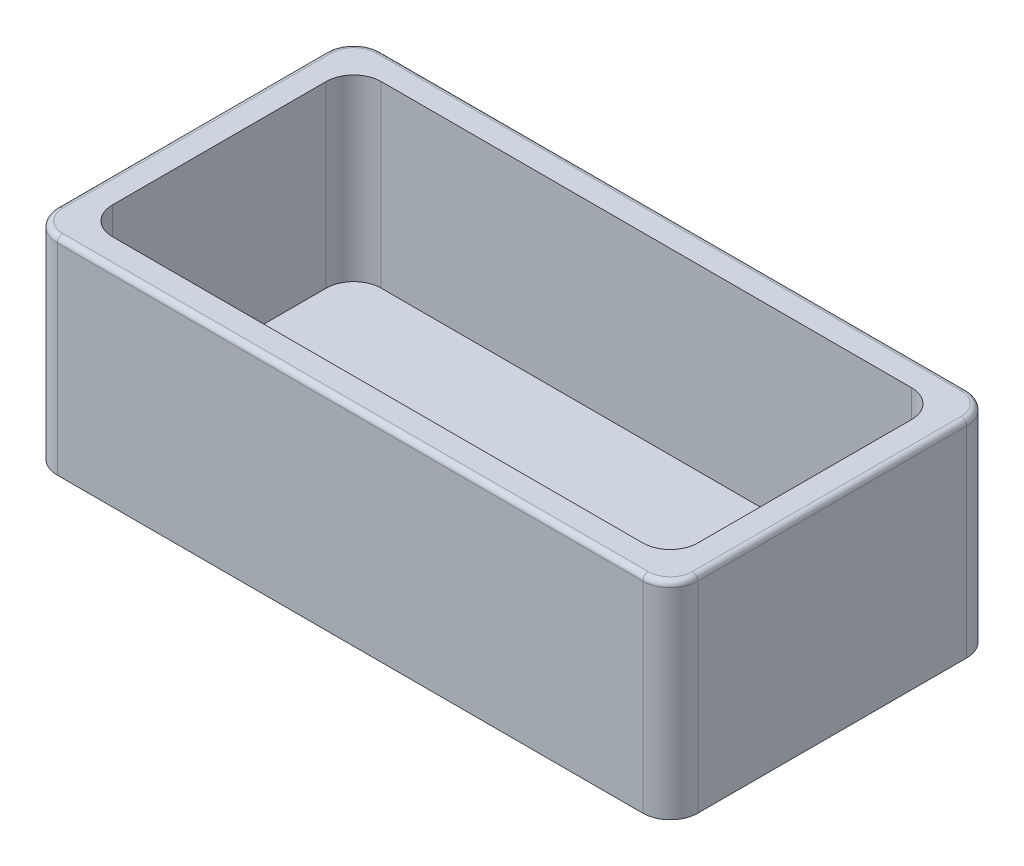
SolidWorks part; units mm, degrees
ref_plane "Front Plane" through (0, 0, 0) normal (0, 0, 1) x (1, 0, 0)
ref_plane "Top Plane" through (0, 0, 0) normal (0, 1, 0) x (1, 0, 0)
ref_plane "Right Plane" through (0, 0, 0) normal (1, 0, 0) x (0, 0, -1)
sketch "Sketch1" plane through (0, 0, 0) normal (0, 1, 0) x (1, 0, 0)
  line L1 (-116.6006, 55.8103) -> (116.0074, 55.8103)
  line L2 (-116.6006, 55.8103) -> (-116.6006, -61.8132)
  line L3 (-116.6006, -61.8132) -> (116.0074, -61.8132)
  line L4 (116.0074, 55.8103) -> (116.0074, -61.8132)
extrude "Boss-Extrude1" add sketch "Sketch1" along normal blind 75
shell "Shell13" thickness 10 removed face at (-0.2966, 75, 3.0015)
fillet "Fillet5" radius 10 4 edges at (106.0074, 42.5, -45.8103) (106.0074, 42.5, 51.8132) (-106.6006, 42.5, -45.8103) (-106.6006, 42.5, 51.8132)
fillet "Fillet8" radius 2 4 edges at (-0.2966, 75, -55.8103) (-116.6006, 75, 3.0015) (-0.2966, 75, 61.8132) (116.0074, 75, 3.0015)
fillet "Fillet9" radius 10 8 edges at (115.4216, 74.4142, 61.2274) (-116.0148, 74.4142, 61.2274) (-116.0148, 74.4142, -55.2245) (115.4216, 74.4142, -55.2245) (116.0074, 36.5, 61.8132) (-116.6006, 36.5, 61.8132) (-116.6006, 36.5, -55.8103) (116.0074, 36.5, -55.8103)
